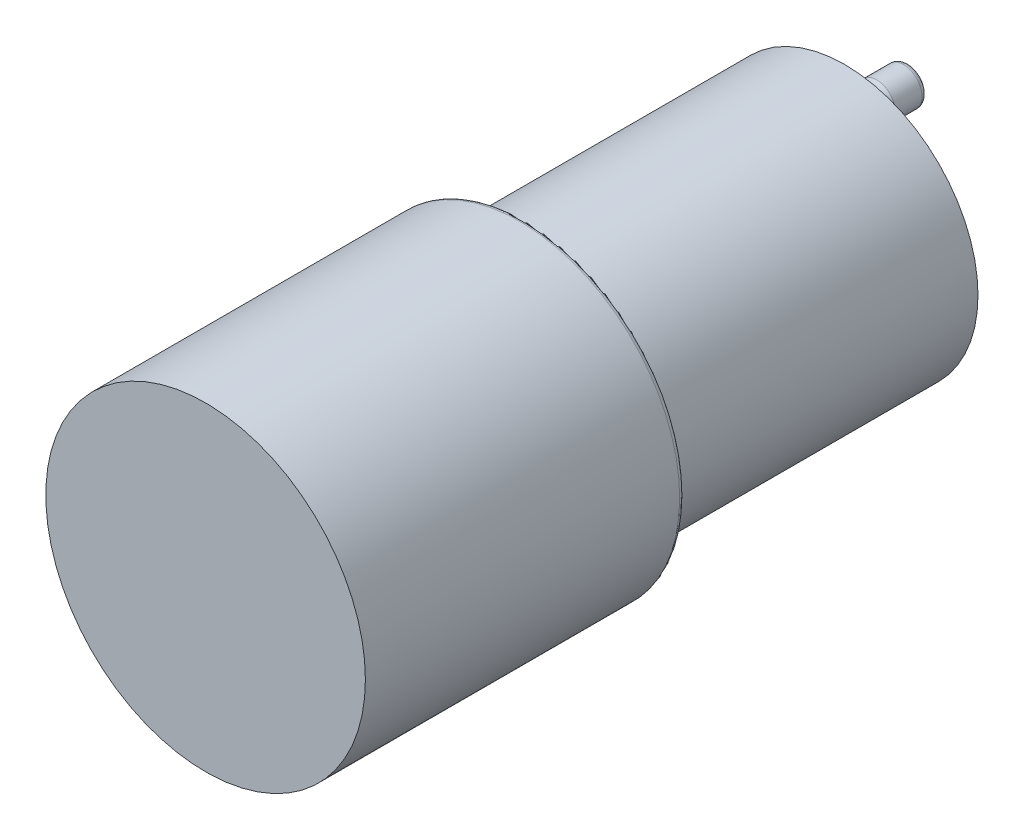
SolidWorks part; units mm, degrees
material "冷拉钢丝 45"
ref_plane "前视基准面" through (0, 0, 0) normal (0, 0, 1) x (1, 0, 0)
ref_plane "上视基准面" through (0, 0, 0) normal (0, 1, 0) x (1, 0, 0)
ref_plane "右视基准面" through (0, 0, 0) normal (1, 0, 0) x (0, 0, -1)
sketch "草图1" plane through (0, 0, 0) normal (0, 0, 1) x (1, 0, 0)
  circle A0 centre (0, 0) radius 12.5
  dimension "D1" = 25
extrude "凸台-拉伸1" add sketch "草图1" along normal blind 60
sketch "草图3" plane through (0, 0, 0) normal (0, 0, -1) x (-1, 0, 0)
  line L0 (0, 0) -> (0, 8) construction
  circle A0 centre (0, 0) radius 1.5
  circle A1 centre (0, 8) radius 1.5
  dimension "D1" = 3
  dimension "D3" = 3
  dimension "D2" = 8
extrude "凸台-拉伸2" add sketch "草图3" along normal blind 3
sketch "草图4" plane through (0, 0, -3) normal (0, 0, -1) x (-1, 0, 0)
  circle A0 centre (0, 0) radius 1.75
  circle A1 centre (0, 8) radius 1.75
  dimension "D1" = 3.5
  dimension "D2" = 3.5
extrude "凸台-拉伸3" add sketch "草图4" along normal blind 3
fillet "圆角1" radius 10 1 edges at (-1.5, 8, -3)
fillet "圆角2" radius 10 1 edges at (-1.5, 0, -3)
fillet "圆角3" radius 0.5 2 edges at (-1.75, 0, -6) (-1.75, 8, -6)
sketch "草图5" plane through (0, 0, 60) normal (0, 0, 1) x (1, 0, 0)
  circle A0 centre (0, 0) radius 15
  dimension "D1" = 30
extrude "凸台-拉伸4" add sketch "草图5" against normal blind 30
fillet "圆角4" radius 0.5 1 edges at (12.5, 0, 30)
fillet "圆角5" radius 0.5 1 edges at (15, 0, 30)
